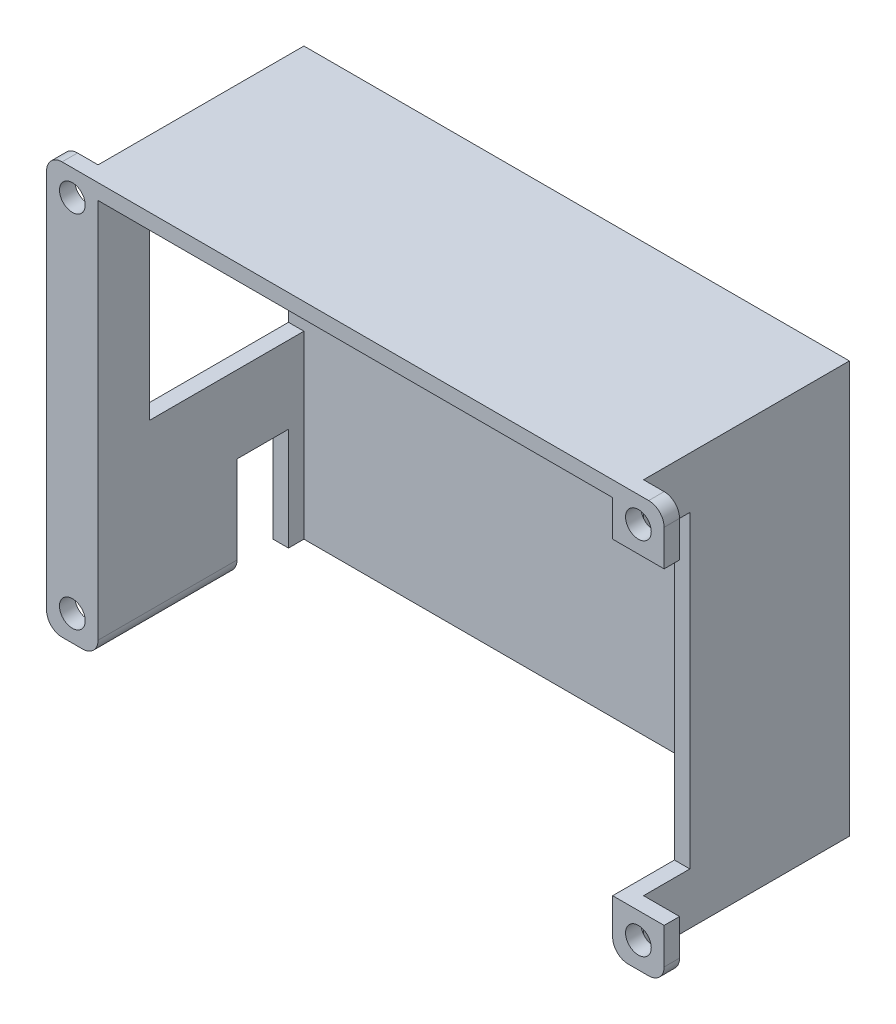
SolidWorks part; units mm, degrees
ref_plane "Front Plane" through (0, 0, 0) normal (0, 0, 1) x (1, 0, 0)
ref_plane "Top Plane" through (0, 0, 0) normal (0, 1, 0) x (1, 0, 0)
ref_plane "Right Plane" through (0, 0, 0) normal (1, 0, 0) x (0, 0, -1)
sketch "Sketch2" plane through (0, 0, 0) normal (0, 0, 1) x (1, 0, 0)
  line L1 (15.306, 62.8336) -> (75.306, 62.8336)
  line L2 (15.306, 62.8336) -> (15.306, 22.8336)
  line L3 (15.306, 22.8336) -> (75.306, 22.8336)
  line L4 (75.306, 62.8336) -> (75.306, 22.8336)
  circle A0 centre (17.806, 60.3336) radius 1.25
  circle A1 centre (17.806, 25.3336) radius 1.25
  circle A2 centre (72.806, 25.3336) radius 1.25
  circle A3 centre (72.806, 60.3336) radius 1.25
  dimension "D2" = 2.5
  dimension "D1" = 60
  dimension "D3" = 40
  dimension "D4" = 2.5
  dimension "D5" = 2.5
  dimension "D6" = 2.5
  dimension "D7" = 2.5
extrude "Boss-Extrude3" add sketch "Sketch2" along normal blind 1.5
sketch "Sketch3" plane through (0, 0, 0) normal (0, 0, -1) x (-1, 0, 0)
  line L0 (-75.306, 62.8336) -> (-15.306, 62.8336) construction
  line L1 (-71.806, 62.8336) -> (-18.806, 62.8336)
  line L2 (-71.806, 62.8336) -> (-71.806, 22.8336)
  line L3 (-71.806, 22.8336) -> (-18.806, 22.8336)
  line L4 (-18.806, 62.8336) -> (-18.806, 22.8336)
  line L6 (-15.306, 22.8336) -> (-75.306, 22.8336) construction
  line L7 (-75.306, 22.8336) -> (-75.306, 62.8336) construction
  line L8 (-15.306, 62.8336) -> (-15.306, 22.8336) construction
  dimension "D1" = 0
  dimension "D2" = 0
  dimension "D3" = 3.5
  dimension "D4" = 3.5
extrude "Boss-Extrude4" add sketch "Sketch3" along normal blind 20
sketch "Sketch7" plane through (0, 0, 1.5) normal (0, 0, 1) x (1, 0, 0)
  line L0 (75.306, 62.8336) -> (15.306, 62.8336) construction
  line L1 (20.306, 61.3336) -> (70.306, 61.3336)
  line L2 (20.306, 61.3336) -> (20.306, 22.8336)
  line L3 (20.306, 22.8336) -> (70.306, 22.8336)
  line L4 (70.306, 61.3336) -> (70.306, 22.8336)
  line L5 (15.306, 62.8336) -> (15.306, 22.8336) construction
  line L6 (75.306, 22.8336) -> (75.306, 62.8336) construction
  line L7 (15.306, 22.8336) -> (75.306, 22.8336) construction
  dimension "D1" = 1.5
  dimension "D2" = 5
  dimension "D3" = 5
  dimension "D4" = 0
extrude "Cut-Extrude4" cut sketch "Sketch7" against normal blind 20
sketch "Sketch8" plane through (71.806, 0, 0) normal (1, 0, 0) x (0, 0, -1)
  line L1 (-1.5, 57.8336) -> (4.5, 57.8336)
  line L2 (-1.5, 57.8336) -> (-1.5, 27.8336)
  line L3 (-1.5, 27.8336) -> (4.5, 27.8336)
  line L4 (4.5, 57.8336) -> (4.5, 27.8336)
  line L7 (20, 62.8336) -> (0, 62.8336) construction
  line L8 (20, 22.8336) -> (0, 22.8336) construction
  line L9 (-1.5, 22.8336) -> (-1.5, 62.8336) construction
  dimension "D2" = 6
  dimension "D1" = 5
  dimension "D3" = 5
extrude "Cut-Extrude5" cut sketch "Sketch8" against normal blind 12.5 and the other way blind 10
sketch "Sketch11" plane through (18.806, 0, 0) normal (-1, 0, 0) x (0, 0, 1)
  line L1 (0, 62.8336) -> (-5, 62.8336)
  line L2 (0, 62.8336) -> (0, 57.8336)
  line L3 (0, 57.8336) -> (-5, 57.8336)
  line L4 (-5, 62.8336) -> (-5, 57.8336)
  line L5 (0, 22.8336) -> (-5, 22.8336)
  line L6 (0, 22.8336) -> (0, 27.8336)
  line L7 (0, 27.8336) -> (-5, 27.8336)
  line L8 (-5, 22.8336) -> (-5, 27.8336)
  dimension "D1" = 5
  dimension "D2" = 5
extrude "Cut-Extrude8" [suppressed] cut sketch "Sketch11" against normal blind 2.5
sketch "Sketch17" plane through (18.806, 0, 0) normal (-1, 0, 0) x (0, 0, 1)
  line L0 (-20, 22.8336) -> (-20, 62.8336) construction
  line L1 (-18.5, 40.3336) -> (-3.5, 40.3336)
  line L2 (-18.5, 40.3336) -> (-18.5, 57.8336)
  line L3 (-18.5, 57.8336) -> (-3.5, 57.8336)
  line L4 (-3.5, 40.3336) -> (-3.5, 57.8336)
  line L5 (-20, 22.8336) -> (0, 22.8336) construction
  line L6 (1.5, 62.8336) -> (0, 62.8336) construction
  line L7 (-17, 22.8336) -> (-12, 22.8336)
  line L8 (-17, 22.8336) -> (-17, 32.8336)
  line L9 (-17, 32.8336) -> (-12, 32.8336)
  line L10 (-12, 22.8336) -> (-12, 32.8336)
  dimension "D1" = 5
  dimension "D2" = 17.5
  dimension "D3" = 15
  dimension "D4" = 1.5
  dimension "D5" = 10
  dimension "D6" = 3
  dimension "D7" = 5
extrude "Cut-Extrude13" cut sketch "Sketch17" against normal blind 2.5
sketch "Sketch19" plane through (0, 0, 0) normal (0, 0, -1) x (-1, 0, 0)
  line L0 (-70.306, 61.3336) -> (-70.306, 22.8336) construction
  line L1 (-71.806, 33.3336) -> (-73.806, 33.3336)
  line L2 (-71.806, 33.3336) -> (-71.806, 31.3336)
  line L3 (-71.806, 31.3336) -> (-73.806, 31.3336)
  line L4 (-73.806, 33.3336) -> (-73.806, 31.3336)
  line L5 (-71.806, 22.8336) -> (-75.306, 22.8336) construction
  line L6 (-75.306, 62.8336) -> (-71.806, 62.8336) construction
  line L7 (-71.806, 57.8336) -> (-73.806, 57.8336)
  line L8 (-71.806, 57.8336) -> (-71.806, 55.8336)
  line L9 (-71.806, 55.8336) -> (-73.806, 55.8336)
  line L10 (-73.806, 57.8336) -> (-73.806, 55.8336)
  dimension "D1" = 1.5
  dimension "D2" = 2
  dimension "D3" = 8.5
  dimension "D4" = 2
  dimension "D5" = 5
extrude "Boss-Extrude5" [suppressed] add sketch "Sketch19" along normal blind 12.5
fillet "Fillet1" radius 1.5 6 edges at (15.306, 22.8336, 0.75) (20.306, 22.8336, -5.25) (15.306, 62.8336, 0.75) (75.306, 62.8336, 0.75) (75.306, 22.8336, 0.75) (70.306, 22.8336, -8.5)
fillet "Fillet2" [suppressed] radius 1.5
fillet "Fillet4" [suppressed] radius 0.5
fillet "Fillet5" [suppressed] radius 1.5
equation "\"D3@Sketch8\"=\"D1@Sketch8\""
